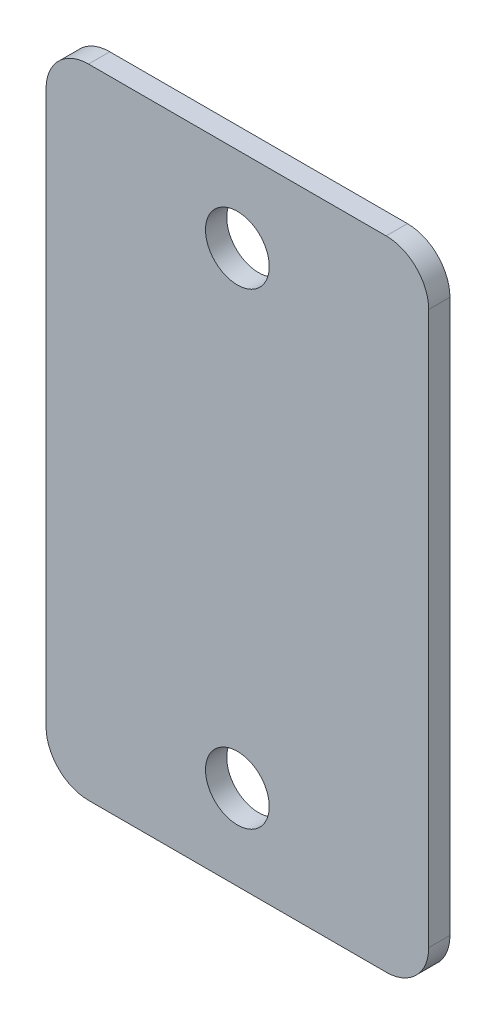
SolidWorks part; units mm, degrees
material "ABS"
ref_plane "Front Plane" through (0, 0, 0) normal (0, 0, 1) x (1, 0, 0)
ref_plane "Top Plane" through (0, 0, 0) normal (0, 1, 0) x (1, 0, 0)
ref_plane "Right Plane" through (0, 0, 0) normal (1, 0, 0) x (0, 0, -1)
sketch "Sketch1" plane through (0, 0, 0) normal (0, 0, 1) x (1, 0, 0)
  line L0 (0, 0) -> (18, 0) construction
  line L1 (-18, -30) -> (18, -30)
  line L2 (-18, -30) -> (-18, 30)
  line L3 (-18, 30) -> (18, 30)
  line L4 (18, -30) -> (18, 30)
  line L5 (-18, -30) -> (18, 30) construction
  line L6 (-18, 30) -> (18, -30) construction
  point P0 (0, 0)
  point P6 (0, 22)
  point P9 (0, -22)
  dimension "D1" = 36
  dimension "D2" = 60
  dimension "D3" = 8
extrude "Boss-Extrude1" add sketch "Sketch1" along normal mid plane 2
hole_wizard "Ø6.0mm Dowel Hole1" positions "Sketch2" profile "Sketch3" hole size "Ø6.0" standard "ANSI Metric" end condition through all
sketch "Sketch2" plane through (0, 0, 1) normal (0, 0, 1) x (1, 0, 0)
  point P0 (0, 22)
  point P3 (0, -22)
sketch "Sketch3" plane through (0, 22, 1) normal (1, 0, 0) x (0, -1, 0)
  line L0 (0, 0) -> (0, 2)
  line L1 (0, 2) -> (3, 2)
  line L2 (3, 2) -> (3, 0)
  line L5 (3, 0) -> (0, 0)
  line L11 (0, -6.35) -> (0, 107.95) construction
  dimension "Thru Hole Dia." = 6
  dimension "Thru Hole Depth" = 2
fillet "Fillet1" radius 4 4 edges at (18, -30, 0) (-18, -30, 0) (18, 30, 0) (-18, 30, 0)
